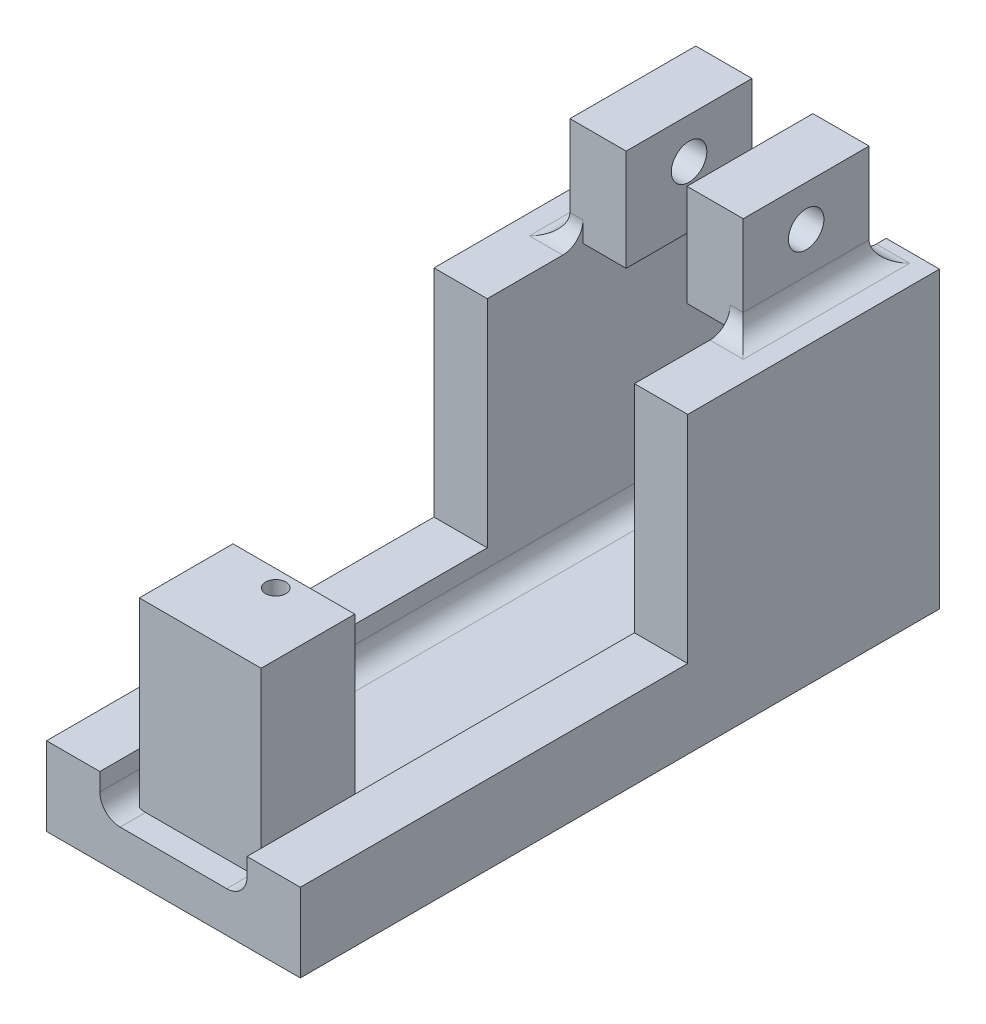
SolidWorks part; units mm, degrees
ref_plane "Front Plane" through (0, 0, 0) normal (0, 0, 1) x (1, 0, 0)
ref_plane "Top Plane" through (0, 0, 0) normal (0, 1, 0) x (1, 0, 0)
ref_plane "Right Plane" through (0, 0, 0) normal (1, 0, 0) x (0, 0, -1)
sketch "Sketch1" plane through (0, 0, 0) normal (0, 1, 0) x (1, 0, 0)
  line L1 (12.5, -40) -> (-12.5, -40)
  line L2 (12.5, -40) -> (12.5, 40)
  line L3 (12.5, 40) -> (-12.5, 40)
  line L4 (-12.5, -40) -> (-12.5, 40)
  line L5 (12.5, -40) -> (-12.5, 40) construction
  line L6 (12.5, 40) -> (-12.5, -40) construction
  point P0 (0, 0)
  dimension "D1" = 25
  dimension "D2" = 80
extrude "Boss-Extrude1" add sketch "Sketch1" along normal blind 4 contours L3 L4 L1 L2
sketch "Sketch2" plane through (0, 4, 0) normal (0, 1, 0) x (1, 0, 0)
  line L0 (12.5, -40) -> (-12.5, -40) construction
  line L1 (-12.5, 40) -> (-7.25, 40)
  line L2 (-12.5, 40) -> (-12.5, -40)
  line L3 (-12.5, -40) -> (-7.25, -40)
  line L4 (-7.25, 40) -> (-7.25, -40)
  dimension "D1" = 5.25
extrude "Boss-Extrude2" add sketch "Sketch2" along normal blind 25
mirror "Mirror1" about plane through (0, 0, 0) normal (1, 0, 0) of "Boss-Extrude2"
fillet "Fillet1" radius 2 2 edges at (7.25, 4, 0) (-7.25, 4, 0)
ref_plane "Plane1" through (0, 29, 0) normal (0, 1, 0) x (1, 0, 0)
sketch "Sketch4" plane through (0, 29, 0) normal (0, 1, 0) x (1, 0, 0)
  line L0 (0, -15.95) -> (0, 15.95) construction
  line L4 (-3, 20) -> (-3, 7.6016)
  line L5 (8.5368, 7.6016) -> (3, 7.6016)
  line L6 (3, 20) -> (3, 7.6016)
  line L11 (-8.5368, 20) -> (-8.5368, 7.6016)
  line L12 (-8.5368, 20) -> (-3, 20)
  line L13 (-8.5368, 7.6016) -> (-3, 7.6016)
  line L14 (8.5368, 20) -> (3, 20)
  line L15 (8.5368, 20) -> (8.5368, 7.6016)
extrude "Boss-Extrude4" add sketch "Sketch4" along normal blind 10
sketch "Sketch5" plane through (12.5, 0, 0) normal (1, 0, 0) x (0, 0, -1)
  circle A0 centre (13.8008, 35) radius 1.75
  dimension "D1" = 3.5
extrude "Cut-Extrude1" cut sketch "Sketch5" against normal through all
sketch "Sketch6" plane through (0, 4, 0) normal (0, 1, 0) x (1, 0, 0)
  line L0 (5.25, -40) -> (-5.25, -40) construction
  line L1 (6.1393, -37.5) -> (-5.8607, -37.5)
  line L2 (6.1393, -37.5) -> (6.1393, -28.2706)
  line L3 (6.1393, -28.2706) -> (-5.8607, -28.2706)
  line L4 (-5.8607, -37.5) -> (-5.8607, -28.2706)
  line L5 (6.1393, -37.5) -> (-5.8607, -28.2706) construction
  line L6 (6.1393, -28.2706) -> (-5.8607, -37.5) construction
  point P0 (0.1393, -32.8853)
  dimension "D1" = 2.5
  dimension "D2" = 12
extrude "Boss-Extrude5" add sketch "Sketch6" along normal blind 18
sketch "Sketch7" plane through (0, 22, 0) normal (0, 1, 0) x (1, 0, 0)
  line L0 (6.1393, -28.2706) -> (-5.8607, -28.2706) construction
  circle A0 centre (0, -29.9206) radius 1
  dimension "D1" = 2
  dimension "D2" = 1.65
extrude "Cut-Extrude2" cut sketch "Sketch7" against normal blind 8
fillet "Fillet2" radius 2 6 edges at (-8.5368, 29, -13.8008) (8.5368, 29, -13.8008) (-7.8934, 29, -20) (7.8934, 29, -20) (7.8934, 29, -7.6016) (-7.8934, 29, -7.6016)
sketch "Sketch8" plane through (0, 29, 0) normal (0, 1, 0) x (1, 0, 0)
  line L0 (-12.5, 40) -> (-12.5, -40) construction
  line L1 (-12.5, 22.969) -> (12.5, 22.969)
  line L2 (-12.5, 22.969) -> (-12.5, 40)
  line L3 (-12.5, 40) -> (12.5, 40)
  line L4 (12.5, 22.969) -> (12.5, 40)
extrude "Cut-Extrude3" cut sketch "Sketch8" against normal through all
sketch "Sketch11" plane through (-12.5, 0, 0) normal (-1, 0, 0) x (0, 0, 1)
  line L0 (-22.969, 29) -> (40, 29) construction
  line L1 (1.8298, 29) -> (40.0095, 29)
  line L2 (1.8298, 29) -> (1.8298, 7.7431)
  line L3 (1.8298, 7.7431) -> (40.0095, 7.7431)
  line L4 (40.0095, 29) -> (40.0095, 7.7431)
extrude "Cut-Extrude4" cut sketch "Sketch11" against normal blind 6
mirror "Mirror2" about plane through (0, 0, 0) normal (1, 0, 0) of "Cut-Extrude4"
sketch "Sketch12" plane through (0, 4, 0) normal (0, 1, 0) x (1, 0, 0)
  line L1 (4.2579, 10.8089) -> (-4.2579, 10.8089)
  line L2 (4.2579, 10.8089) -> (4.2579, 20.6374)
  line L3 (4.2579, 20.6374) -> (-4.2579, 20.6374)
  line L4 (-4.2579, 10.8089) -> (-4.2579, 20.6374)
  line L5 (4.2579, 10.8089) -> (-4.2579, 20.6374) construction
  line L6 (4.2579, 20.6374) -> (-4.2579, 10.8089) construction
extrude "Cut-Extrude5" cut sketch "Sketch12" against normal through all
